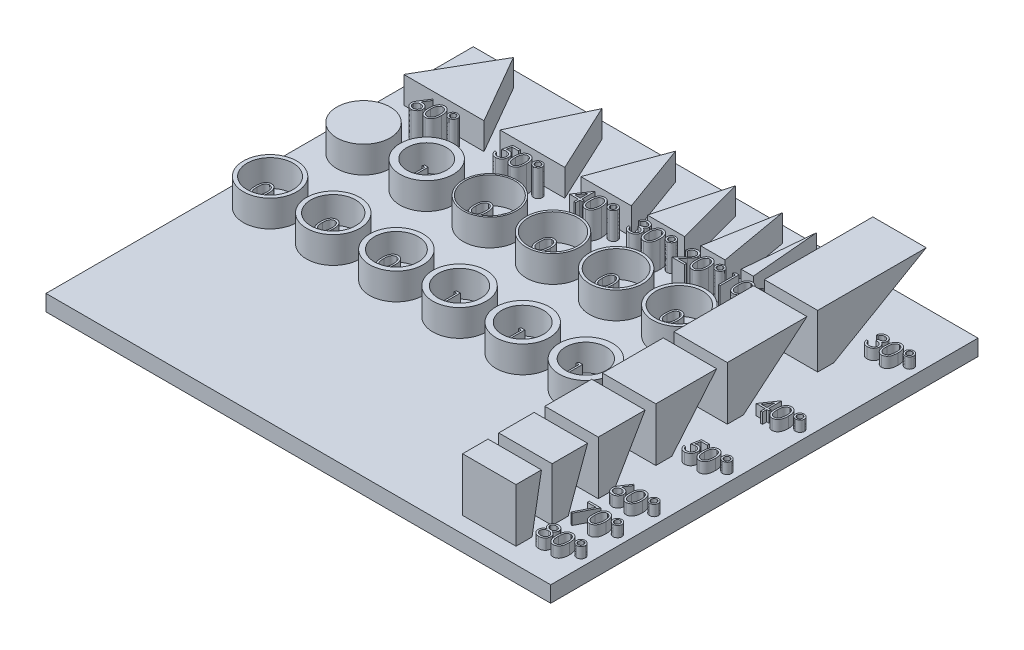
SolidWorks part; units mm, degrees
ref_plane "Front Plane" through (0, 0, 0) normal (0, 0, 1) x (1, 0, 0)
ref_plane "Top Plane" through (0, 0, 0) normal (0, 1, 0) x (1, 0, 0)
ref_plane "Right Plane" through (0, 0, 0) normal (1, 0, 0) x (0, 0, -1)
sketch "Sketch1" plane through (0, 0, 0) normal (0, 1, 0) x (1, 0, 0)
  line L1 (-75, 40) -> (75, 40)
  line L2 (-75, 40) -> (-75, -40)
  line L3 (-75, -40) -> (75, -40)
  line L4 (75, 40) -> (75, -40)
  line L5 (-75, 40) -> (75, -40) construction
  line L6 (-75, -40) -> (75, 40) construction
  point P0 (0, 0)
  dimension "D1" = 150
  dimension "D2" = 80
extrude "Boss-Extrude1" add sketch "Sketch1" along normal blind 3
sketch "Sketch2" plane through (0, 3, 0) normal (0, 1, 0) x (1, 0, 0)
  line L0 (-72, 24) -> (-64.4944, 37)
  line L1 (-64.4944, 37) -> (-56.9889, 24)
  line L2 (-56.9889, 24) -> (-72, 24)
  line L3 (-64.4944, 37) -> (-64.4944, 24) construction
  line L4 (-53.9889, 24) -> (-47.9269, 37)
  line L5 (-47.9269, 37) -> (-41.8649, 24)
  line L6 (-41.8649, 24) -> (-53.9889, 24)
  line L7 (-47.9269, 37) -> (-47.9269, 24) construction
  line L8 (-38.8649, 24) -> (-34.1333, 37)
  line L9 (-34.1333, 37) -> (-29.4017, 24)
  line L10 (-29.4017, 24) -> (-38.8649, 24)
  line L11 (-34.1333, 37) -> (-34.1333, 24) construction
  line L12 (-26.4017, 24) -> (-22.9183, 37)
  line L13 (-22.9183, 37) -> (-19.435, 24)
  line L14 (-19.435, 24) -> (-26.4017, 24)
  line L15 (-22.9183, 37) -> (-22.9183, 24) construction
  line L16 (-16.435, 24) -> (-14.1427, 37)
  line L17 (-14.1427, 37) -> (-11.8505, 24)
  line L18 (-11.8505, 24) -> (-16.435, 24)
  line L19 (-14.1427, 37) -> (-14.1427, 24) construction
  line L20 (-8.8505, 24) -> (-7.7131, 37)
  line L21 (-7.7131, 37) -> (-6.5758, 24)
  line L22 (-6.5758, 24) -> (-8.8505, 24)
  line L23 (-7.7131, 37) -> (-7.7131, 24) construction
  line L25 (-75, 40) -> (-75, -40) construction
  line L26 (75, 40) -> (-75, 40) construction
  dimension "D1" = 60
  dimension "D2" = 50
  dimension "D3" = 40
  dimension "D4" = 30
  dimension "D5" = 20
  dimension "D6" = 10
  dimension "D7" = 3
  dimension "D8" = 3
  dimension "D9" = 3
  dimension "D10" = 3
  dimension "D11" = 3
  dimension "D12" = 3
  dimension "D13" = 3
  dimension "D14" = 13
extrude "Boss-Extrude2" add sketch "Sketch2" along normal blind 5
sketch "Sketch3" plane through (0, 3, 0) normal (0, 1, 0) x (1, 0, 0)
  text T0 "60°"
extrude "Boss-Extrude3" add sketch "Sketch3" along normal blind 5
sketch "Sketch5" plane through (0, 3, 0) normal (0, 1, 0) x (1, 0, 0)
  text T0 "50°"
extrude "Boss-Extrude4" add sketch "Sketch5" along normal blind 5
sketch "Sketch6" plane through (0, 3, 0) normal (0, 1, 0) x (1, 0, 0)
  text T0 "40°"
extrude "Boss-Extrude5" add sketch "Sketch6" along normal blind 5
sketch "Sketch7" plane through (0, 3, 0) normal (0, 1, 0) x (1, 0, 0)
  text T0 "30°"
extrude "Boss-Extrude6" add sketch "Sketch7" along normal blind 5
sketch "Sketch8" plane through (0, 3, 0) normal (0, 1, 0) x (1, 0, 0)
  text T0 "20°"
extrude "Boss-Extrude7" add sketch "Sketch8" along normal blind 5
sketch "Sketch9" plane through (0, 3, 0) normal (0, 1, 0) x (1, 0, 0)
  text T0 "10°"
extrude "Boss-Extrude8" add sketch "Sketch9" along normal blind 5
sketch "Sketch10" plane through (0, 3, 0) normal (0, 1, 0) x (1, 0, 0)
  line L0 (-68, 12.4511) -> (-56.1746, 12.4511) construction
  line L1 (-56.1746, 12.4511) -> (-44.3492, 12.4511) construction
  line L2 (-44.3492, 12.4511) -> (-32.5239, 12.4511) construction
  line L3 (-32.5239, 12.4511) -> (-20.6985, 12.4511) construction
  line L4 (-20.6985, 12.4511) -> (-8.8731, 12.4511) construction
  line L5 (-68, -5.0472) -> (-56.1746, -5.0472) construction
  line L6 (-56.1746, -5.0472) -> (-44.3492, -5.0472) construction
  line L7 (-44.3492, -5.0472) -> (-32.5239, -5.0472) construction
  line L8 (-32.5239, -5.0472) -> (-20.6985, -5.0472) construction
  line L9 (-20.6985, -5.0472) -> (-8.8731, -5.0472) construction
  line L10 (-75, 40) -> (-75, -40) construction
  line L19 (74.3, -39.3) -> (74.3, 39.3)
  line L20 (74.3, 39.3) -> (-74.3, 39.3)
  line L21 (-74.3, 39.3) -> (-74.3, -39.3)
  line L22 (-74.3, -39.3) -> (74.3, -39.3)
  line L23 (74.3, -39.3) -> (74.3, 39.3)
  line L24 (74.3, 39.3) -> (-74.3, 39.3)
  line L25 (-74.3, 39.3) -> (-74.3, -39.3)
  line L26 (-74.3, -39.3) -> (74.3, -39.3)
  circle A0 centre (-68, 12.4511) radius 5
  circle A1 centre (-56.1746, 12.4511) radius 5
  circle A2 centre (-44.3492, 12.4511) radius 5
  circle A4 centre (-56.1746, 12.4511) radius 3.7
  circle A5 centre (-44.3492, 12.4511) radius 4.7
  circle A6 centre (-32.5239, 12.4511) radius 5
  circle A7 centre (-20.6985, 12.4511) radius 5
  circle A8 centre (-32.5239, 12.4511) radius 4.6
  circle A9 centre (-20.6985, 12.4511) radius 4.5
  circle A10 centre (-8.8731, 12.4511) radius 5
  circle A11 centre (-8.8731, 12.4511) radius 4.4
  circle A12 centre (-68, -5.0472) radius 5
  circle A13 centre (-56.1746, -5.0472) radius 5
  circle A14 centre (-44.3492, -5.0472) radius 5
  circle A15 centre (-32.5239, -5.0472) radius 5
  circle A16 centre (-20.6985, -5.0472) radius 5
  circle A17 centre (-8.8731, -5.0472) radius 5
  circle A18 centre (-68, -5.0472) radius 4.3
  circle A19 centre (-56.1746, -5.0472) radius 4.2
  circle A20 centre (-44.3492, -5.0472) radius 4.1
  circle A21 centre (-32.5239, -5.0472) radius 4
  circle A22 centre (-20.6985, -5.0472) radius 3.9
  circle A23 centre (-8.8731, -5.0472) radius 3.8
  dimension "D1" = 10
  dimension "D2" = 10
  dimension "D3" = 10
  dimension "D7" = 10
  dimension "D8" = 10
  dimension "D11" = 0.6
  dimension "D12" = 10
  dimension "D13" = 7
  dimension "D9" = 0.4
  dimension "D14" = 7
  dimension "D5" = 1.3
  dimension "D6" = 0.3
  dimension "D10" = 0.5
  dimension "D15" = 0.7
  dimension "D16" = 0.7
  dimension "D17" = 0.8
  dimension "D18" = 0.9
  dimension "D19" = 1
  dimension "D20" = 1.1
  dimension "D21" = 1.2
extrude "Boss-Extrude9" add sketch "Sketch10" along normal blind 5 contours A2 A5 | A6 A8 | A10 A11 | A17 A23 | A16 A22 | A15 A21 | A14 A20 | A13 A19 | A12 A18 | A0 | A1 | A4 | A9 | A7 region at (-49.2078, 3, -12.4511) region at (-37.3824, 3, -12.4511) region at (-13.7317, 3, -12.4511) region at (-72.8586, 3, 5.0472) region at (-61.0332, 3, 5.0472) region at (-49.2078, 3, 5.0472) region at (-37.3824, 3, 5.0472) region at (-25.5571, 3, 5.0472) region at (-13.7317, 3, 5.0472)
sketch "Sketch11" plane through (0, 3, 0) normal (0, 1, 0) x (1, 0, 0)
  text T0 "0.1 "
  text T1 "1.3"
  text T2 "0.3\r\n"
  text T3 "0.4"
  text T4 "0.5"
  text T5 "0.6"
  text T6 "0.7"
  text T7 "0.8"
  text T8 "0.9"
  text T9 "1.0"
  text T10 "1.1"
  text T11 "1.2\r\n"
extrude "Boss-Extrude10" add sketch "Sketch11" along normal blind 2
sketch "Sketch12" plane through (0, 0, 0) normal (1, 0, 0) x (0, 0, -1)
  line L0 (-34, 3) -> (-32.2367, 13)
  line L1 (-40, 3) -> (40, 3) construction
  line L2 (-32.2367, 13) -> (-37, 13)
  line L3 (-37, 13) -> (-37, 3)
  line L4 (-37, 3) -> (-34, 3)
  line L5 (-40, 3) -> (-40, 0) construction
  line L6 (-30.2367, 3) -> (-30.2367, 13)
  line L7 (-30.2367, 13) -> (-23.597, 13)
  line L8 (-23.597, 13) -> (-27.2367, 3)
  line L9 (-27.2367, 3) -> (-30.2367, 3)
  line L10 (-21.597, 3) -> (-21.597, 13)
  line L11 (-21.597, 13) -> (-12.8235, 13)
  line L12 (-12.8235, 13) -> (-18.597, 3)
  line L13 (-18.597, 3) -> (-21.597, 3)
  line L14 (-10.8235, 3) -> (-10.8235, 13)
  line L15 (-10.8235, 13) -> (0.5675, 13)
  line L16 (0.5675, 13) -> (-7.8235, 3)
  line L17 (-7.8235, 3) -> (-10.8235, 3)
  line L18 (2.5675, 3) -> (2.5675, 13)
  line L19 (2.5675, 13) -> (17.485, 13)
  line L20 (17.485, 13) -> (5.5675, 3)
  line L21 (5.5675, 3) -> (2.5675, 3)
  line L22 (19.485, 13) -> (19.485, 3)
  line L23 (22.9744, 3) -> (21.1332, 3) construction
  line L24 (19.485, 13) -> (39.8055, 13)
  line L25 (39.8055, 13) -> (22.485, 3)
  line L26 (22.485, 3) -> (19.485, 3)
  line L27 (24, 3) -> (37, 3) construction
  dimension "D1" = 80
  dimension "D2" = 3
  dimension "D3" = 3
  dimension "D4" = 10
  dimension "D5" = 70
  dimension "D6" = 2
  dimension "D7" = 2
  dimension "D8" = 60
  dimension "D9" = 50
  dimension "D10" = 2
  dimension "D11" = 2
  dimension "D12" = 40
  dimension "D13" = 2
  dimension "D14" = 30
extrude "Boss-Extrude11" add sketch "Sketch12" along normal blind 10
sketch "Sketch13" plane through (0, 3, 0) normal (0, 1, 0) x (1, 0, 0)
  text T0 "30°\r\n\r\n\r\n40°\r\n\r\n50°\r\n\r\n60°\r\n70°\r\n80°"
extrude "Boss-Extrude12" add sketch "Sketch13" along normal blind 2
sketch "Sketch14" plane through (0, 3, 0) normal (0, 1, 0) x (1, 0, 0)
  line L0 (-75, 40) -> (-75, -40) construction
  line L1 (19.5, 50.3274) -> (101.823, 50.3274)
  line L2 (19.5, 50.3274) -> (19.5, -50.3274)
  line L3 (19.5, -50.3274) -> (101.823, -50.3274)
  line L4 (101.823, 50.3274) -> (101.823, -50.3274)
  line L5 (19.5, 50.3274) -> (101.823, -50.3274) construction
  line L6 (19.5, -50.3274) -> (101.823, 50.3274) construction
  point P0 (60.6615, 0)
  dimension "D1" = 94.5
extrude "Cut-Extrude1" cut sketch "Sketch14" against normal blind 42
equation "\"`30\"=69.3848"
